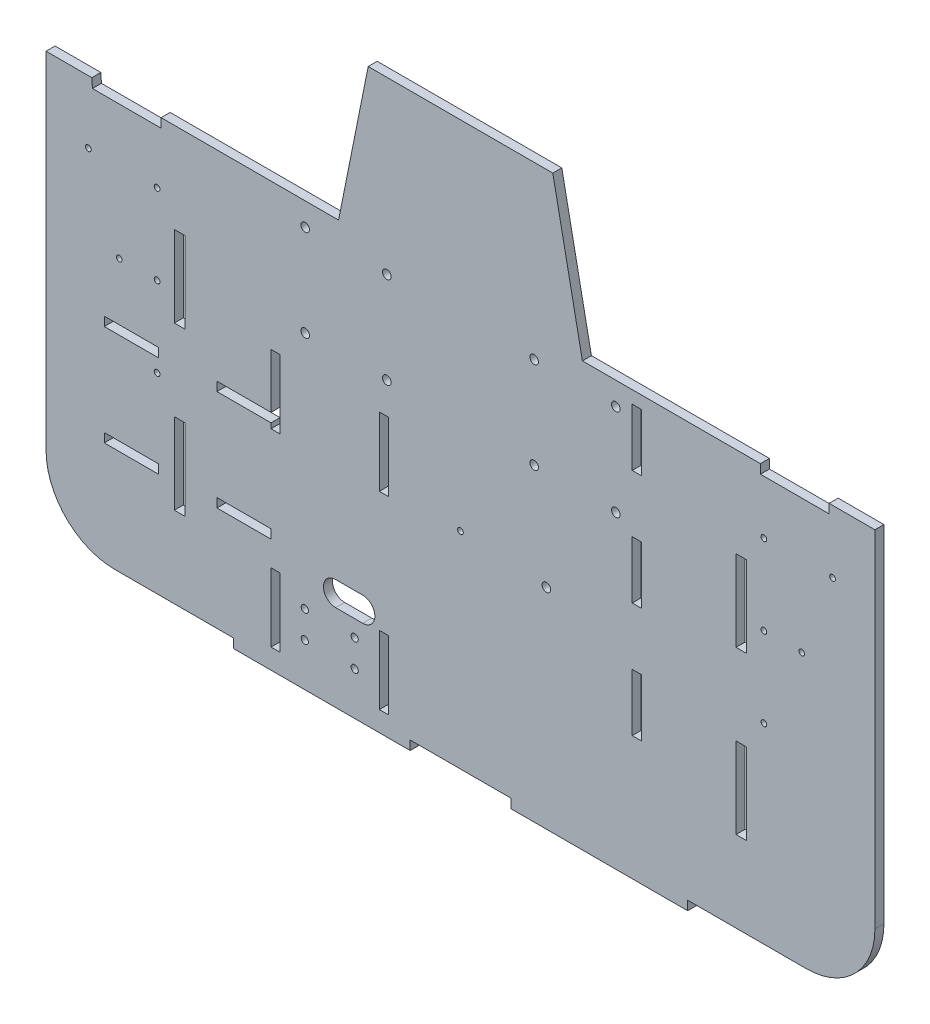
SolidWorks part; units mm, degrees
material "Gillfab4009"
ref_plane "Front Plane" through (0, 0, 0) normal (0, 0, 1) x (1, 0, 0)
ref_plane "Top Plane" through (0, 0, 0) normal (0, 1, 0) x (1, 0, 0)
ref_plane "Right Plane" through (0, 0, 0) normal (1, 0, 0) x (0, 0, -1)
sketch "Sketch2" plane through (0, 0, 0) normal (0, 0, 1) x (1, 0, 0)
  line L0 (-408.9218, 152.7574) -> (-459.7218, 152.7574)
  line L1 (332.7218, 152.7574) -> (135.2505, 152.7574)
  line L2 (-135.2505, 152.7574) -> (-332.1008, 152.7574)
  line L3 (-102.3945, 316.7286) -> (-135.2505, 152.7574)
  line L4 (102.3945, 316.7286) -> (-102.3945, 316.7286)
  line L6 (-459.7218, 152.7574) -> (-459.7218, -230.7826)
  line L7 (459.7218, 152.7574) -> (408.9218, 152.7574)
  line L8 (-303.52, -306.9826) -> (-383.5218, -306.9826)
  line L9 (-252, -317.1426) -> (-55.8292, -317.1426)
  line L11 (408.9218, 142.6164) -> (408.9218, 152.7574)
  line L12 (332.7218, 142.6164) -> (408.9218, 142.6164)
  line L13 (332.7218, 152.7574) -> (332.7218, 142.6164)
  line L14 (-408.3008, 142.6164) -> (-332.1008, 142.6164)
  line L15 (-408.9218, 152.7574) -> (-408.3008, 142.6164)
  line L16 (-332.1008, 142.6164) -> (-332.1008, 152.7574)
  line L17 (305.6323, -37.2346) -> (317.4824, -37.2346)
  line L18 (305.6323, 52.6814) -> (305.6323, -37.2346)
  line L19 (317.4824, 52.6814) -> (305.6323, 52.6814)
  line L20 (317.4824, -37.2346) -> (317.4824, 52.6814)
  line L21 (305.6323, -217.0666) -> (317.4824, -217.0666)
  line L22 (317.4824, -217.0666) -> (317.4824, -127.1506)
  line L23 (317.4824, -127.1506) -> (305.6323, -127.1506)
  line L24 (305.6323, -127.1506) -> (305.6323, -217.0666)
  line L25 (252, -307.3966) -> (202.6964, -307.3966) construction
  line L26 (252, -317.1426) -> (252, -307.3966) construction
  line L27 (0, 316.7286) -> (0, 0) construction
  line L28 (0, 0) -> (0, -307.6709) construction
  line L39 (303.52, -306.9826) -> (383.5218, -306.9826)
  line L44 (-190.5, 75.1277) -> (-190.5, 11.4601) construction
  line L45 (-190.5, -52.225) -> (-190.5, -115.91) construction
  line L46 (-190.5, -179.5951) -> (-190.5, -243.2802) construction
  line L47 (190.5, 75.1277) -> (190.5, 14.3511) construction
  line L48 (190.5, -307.3966) -> (190.5, -243.6941) construction
  line L49 (190.5, 14.3511) -> (190.5, -115.91) construction
  line L52 (190.5, -115.91) -> (190.5, -243.6941) construction
  line L53 (459.7218, 152.7574) -> (459.7218, 465.1616) construction
  line L55 (-335.16, -69.447) -> (-335.16, -79.447)
  line L56 (459.7218, 152.7574) -> (459.7218, -230.7826)
  line L57 (-270.16, -79.447) -> (-210.16, -79.447)
  line L58 (-270.16, -79.447) -> (-270.16, -69.447)
  line L59 (-335.16, -69.447) -> (-395.16, -69.447)
  line L60 (-395.16, -79.447) -> (-210.16, -79.447)
  line L61 (-210.16, -79.447) -> (-210.16, -69.447)
  line L62 (102.3945, 316.7286) -> (135.2505, 152.7574)
  line L63 (-210.16, -69.447) -> (-395.16, -69.447)
  line L64 (-395.16, -69.447) -> (-395.16, -79.447)
  line L65 (-395.16, -79.447) -> (-335.16, -79.447)
  line L67 (-210.16, -69.447) -> (-270.16, -69.447)
  line L68 (-395.16, -69.447) -> (-395.16, -79.447)
  line L69 (-210.16, -191.2542) -> (-395.16, -191.2542) construction
  line L70 (0, -307.6709) -> (0, -629.2246) construction
  line L71 (-210.16, -181.2542) -> (-395.16, -181.2542) construction
  line L72 (-335.16, -191.2542) -> (-335.16, -181.2542) construction
  line L73 (-270.16, -191.2542) -> (-270.16, -181.2542) construction
  line L75 (202.6964, -243.6941) -> (190.5, -243.6941) construction
  line L76 (202.6964, -243.6941) -> (202.6964, -307.3966) construction
  line L79 (200.66, -179.5951) -> (190.5, -179.5951)
  line L80 (190.5, -179.5951) -> (190.5, -115.91)
  line L81 (200.66, -115.91) -> (190.5, -115.91)
  line L82 (200.66, -115.91) -> (200.66, -179.5951)
  line L83 (190.5, -52.225) -> (190.5, 11.4601)
  line L84 (200.66, 11.4601) -> (190.5, 11.4601)
  line L85 (200.66, 11.4601) -> (200.66, -52.225)
  line L86 (200.66, -52.225) -> (190.5, -52.225)
  line L87 (200.66, 138.8128) -> (190.5, 138.8128)
  line L88 (190.5, 75.1277) -> (190.5, 138.8128)
  line L89 (200.66, 75.1277) -> (190.5, 75.1277)
  line L90 (200.66, 138.8128) -> (200.66, 75.1277)
  line L103 (-210.16, -191.4142) -> (-210.16, -294.8827) construction
  line L105 (-210.16, -191.2542) -> (-210.16, -181.2542) construction
  line L106 (-210.16, -79.447) -> (-210.16, -181.2542) construction
  line L107 (-200, -191.4142) -> (-200, -294.8827) construction
  line L108 (-200, -294.8827) -> (-210.16, -294.8827) construction
  line L109 (-200, -218.6827) -> (-210.16, -218.6827) construction
  line L110 (-200, -85.1624) -> (-210.16, -85.1624) construction
  line L111 (-200, -85.1624) -> (-210.16, -85.1624)
  line L112 (-200, -218.6827) -> (-210.16, -218.6827)
  line L113 (-200, -294.8827) -> (-210.16, -294.8827)
  line L114 (-200, -218.6827) -> (-200, -294.8827)
  line L115 (-210.16, -79.447) -> (-210.16, -85.1624)
  line L116 (-210.16, -191.2542) -> (-210.16, -181.2542)
  line L117 (-210.16, -218.6827) -> (-210.16, -294.8827)
  line L118 (-270.16, -191.2542) -> (-270.16, -181.2542)
  line L119 (-335.16, -191.2542) -> (-335.16, -181.2542)
  line L120 (-210.16, -181.2542) -> (-270.16, -181.2542)
  line L121 (-210.16, -191.2542) -> (-270.16, -191.2542)
  line L122 (-395.16, -181.2542) -> (-395.16, -191.2542)
  line L123 (-335.16, -191.2542) -> (-395.16, -191.2542)
  line L124 (-335.16, -181.2542) -> (-395.16, -181.2542)
  line L125 (-210.16, -69.447) -> (-210.16, -8.9624)
  line L126 (-210.16, -8.9624) -> (-200, -8.9624)
  line L127 (-200, -8.9624) -> (-200, -85.1624)
  line L128 (305.6323, -37.2346) -> (305.6323, -217.0666) construction
  line L129 (317.4824, -37.2346) -> (317.4824, -217.0666) construction
  line L130 (-305.6323, -217.0666) -> (-317.4824, -217.0666)
  line L131 (-305.6323, -127.1506) -> (-305.6323, -217.0666)
  line L132 (-90, -218.6827) -> (-90, -294.8827)
  line L133 (-79.84, -218.6827) -> (-90, -218.6827)
  line L134 (-79.84, -294.8827) -> (-79.84, -218.6827)
  line L135 (-90, -294.8827) -> (-79.84, -294.8827)
  line L136 (-90, -218.6827) -> (-90, -294.8827)
  line L137 (-79.84, -218.6827) -> (-90, -218.6827)
  line L138 (-79.84, -294.8827) -> (-79.84, -218.6827)
  line L139 (-90, -294.8827) -> (-79.84, -294.8827)
  line L140 (-90, -8.9624) -> (-90, -85.1624)
  line L141 (-79.84, -8.9624) -> (-90, -8.9624)
  line L142 (-79.84, -85.1624) -> (-79.84, -8.9624)
  line L143 (-90, -85.1624) -> (-79.84, -85.1624)
  line L144 (-90, -8.9624) -> (-90, -85.1624)
  line L145 (-79.84, -8.9624) -> (-90, -8.9624)
  line L146 (-79.84, -85.1624) -> (-79.84, -8.9624)
  line L147 (-90, -85.1624) -> (-79.84, -85.1624)
  line L148 (-317.4824, -127.1506) -> (-305.6323, -127.1506)
  line L149 (-317.4824, -217.0666) -> (-317.4824, -127.1506)
  line L150 (-305.6323, -37.2346) -> (-317.4824, -37.2346)
  line L151 (-317.4824, -37.2346) -> (-317.4824, 52.6814)
  line L152 (-317.4824, 52.6814) -> (-305.6323, 52.6814)
  line L153 (-305.6323, 52.6814) -> (-305.6323, -37.2346)
  line L154 (-183, -317.1426) -> (-183, -226.646) construction
  line L155 (-183, -304.4426) -> (-107.07, -304.4426) construction
  line L156 (-108.5, -207.6709) -> (-138.5, -207.6709) construction
  line L157 (-108.5, -221.1709) -> (-138.5, -221.1709)
  line L158 (-108.5, -194.1709) -> (-138.5, -194.1709)
  line L159 (-90, -191.4142) -> (-90, -294.8827) construction
  line L160 (-145.035, -304.4426) -> (-145.035, -269.4426) construction
  line L161 (-172.69, -269.4426) -> (-117.38, -269.4426) construction
  line L162 (-145.035, -239.4426) -> (-145.035, -269.4426) construction
  line L163 (-172.69, -239.4426) -> (-117.38, -239.4426) construction
  line L164 (-55.8292, -306.9826) -> (55.8292, -306.9826) construction
  line L165 (-55.8292, -306.9826) -> (55.8292, -306.9826)
  line L166 (-55.8292, -306.9826) -> (-55.8292, -317.1426) construction
  line L167 (55.8292, -306.9826) -> (55.8292, -317.1426) construction
  line L168 (-55.8292, -306.9826) -> (-55.8292, -317.1426)
  line L169 (55.8292, -306.9826) -> (55.8292, -317.1426)
  line L170 (303.52, -306.9826) -> (252, -306.9826) construction
  line L171 (-303.52, -306.9826) -> (-252, -306.9826) construction
  line L172 (-252, -306.9826) -> (-252, -317.1426) construction
  line L173 (-252, -306.9826) -> (-252, -317.1426)
  line L174 (-303.52, -306.9826) -> (-252, -306.9826)
  line L175 (303.52, -306.9826) -> (252, -306.9826)
  line L176 (252, -306.9826) -> (252, -317.1426) construction
  line L177 (252, -306.9826) -> (252, -317.1426)
  line L178 (55.8292, -317.1426) -> (252, -317.1426)
  arc A0 (-383.5218, -306.9826) -> (-459.7218, -230.7826) centre (-383.5218, -230.7826) cw
  arc A2 (383.5218, -306.9826) -> (459.7218, -230.7826) centre (383.5218, -230.7826) ccw
  circle A6 centre (336.5503, -94.6874) radius 3.175
  circle A7 centre (378.5738, -5.7874) radius 3.175
  circle A8 centre (336.5503, -5.7874) radius 3.175
  circle A9 centre (336.5503, 83.1126) radius 3.175
  circle A10 centre (412.7503, 83.1126) radius 3.175
  circle A11 centre (-412.7503, 83.1126) radius 3.175
  circle A12 centre (-336.5503, 83.1126) radius 3.175
  circle A13 centre (-336.5503, -5.7874) radius 3.175
  circle A14 centre (-378.5738, -5.7874) radius 3.175
  circle A15 centre (-336.5503, -94.6874) radius 3.175
  circle A18 centre (172.2755, 127.3574) radius 4.7625
  circle A19 centre (172.2755, 25.7574) radius 4.7625
  circle A20 centre (81.7245, 25.7574) radius 4.7625
  circle A21 centre (81.7245, 127.3574) radius 4.7625
  circle A22 centre (-81.7245, 25.7574) radius 4.7625
  circle A23 centre (-81.7245, 127.3574) radius 4.7625
  circle A24 centre (-172.2755, 127.3574) radius 4.7625
  circle A25 centre (-172.2755, 25.7574) radius 4.7625
  circle A26 centre (0, -78.3826) radius 3.175
  circle A28 centre (95.25, -84.7326) radius 4.7625
  arc A29 (-108.5, -221.1709) -> (-108.5, -194.1709) centre (-108.5, -207.6709) ccw
  arc A30 (-138.5, -194.1709) -> (-138.5, -221.1709) centre (-138.5, -207.6709) ccw
  circle A31 centre (-172.69, -239.4426) radius 4
  circle A32 centre (-117.38, -239.4426) radius 4
  circle A33 centre (-117.38, -269.4426) radius 4
  circle A34 centre (-172.69, -269.4426) radius 4
  point P59 (-123.5, -207.6709)
  point P74 (-145.035, -269.4426)
  point P128 (-95, -207.6709)
  point P173 (-145.035, -239.4426)
  dimension "D1" = 76.2
  dimension "D8" = 76.2
  dimension "D21" = 27
  dimension "D22" = 30
  dimension "D33" = 8
  dimension "D3" = 919.4436
  dimension "D4" = 305.6323
  dimension "D5" = 183
  dimension "D6" = 12.7
  dimension "D7" = 152.7574
  dimension "D9" = 75.93
  dimension "D11" = 35
  dimension "D12" = 10.16
  dimension "D13" = 190.5
  dimension "D14" = 190.5
  dimension "D15" = 50.8
  dimension "D16" = 0
  dimension "D17" = 50.8
  dimension "D18" = 76.2
  dimension "D19" = 0
  dimension "D23" = 5
  dimension "D24" = 55.31
  dimension "D25" = 11.8501
  dimension "D26" = 52.6814
  dimension "D27" = 89.916
  dimension "D28" = 89.916
  dimension "D29" = 89.916
  dimension "D30" = 316.7286
  dimension "D31" = 55.31
  dimension "D32" = 30
  dimension "D20" = 0
extrude "Boss-Extrude1" add sketch "Sketch2" against normal blind 10
